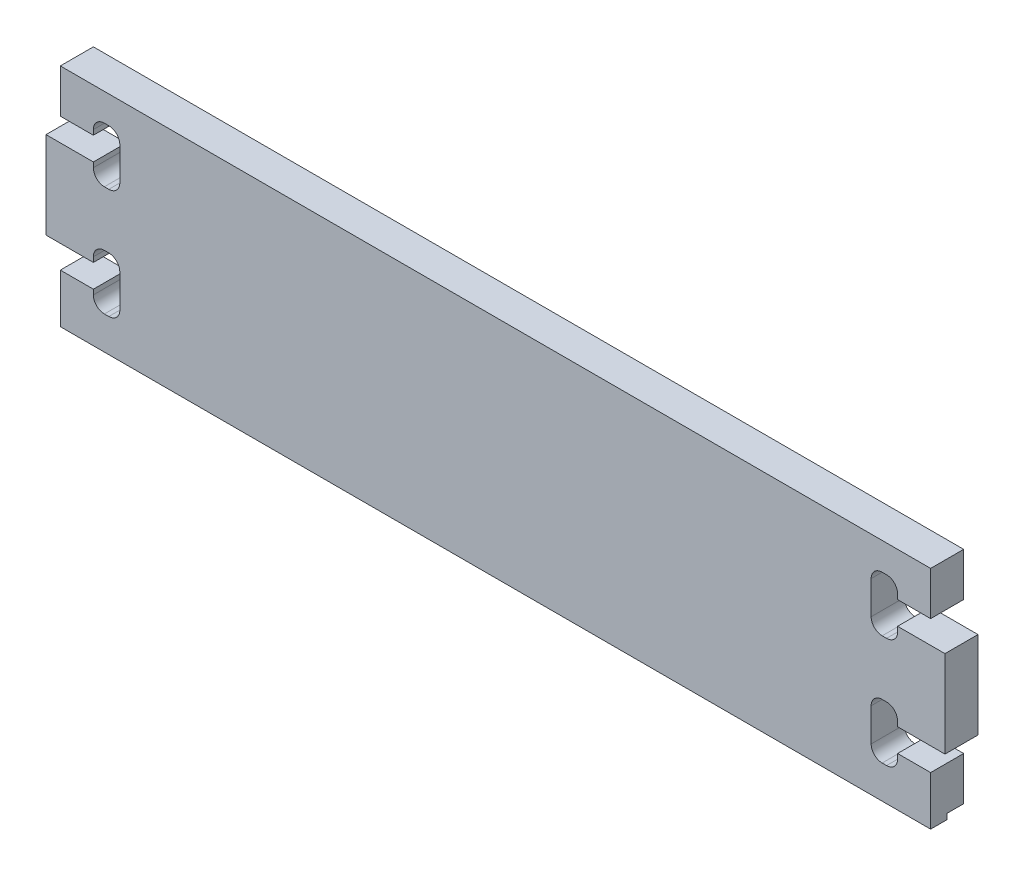
SolidWorks part; units mm, degrees
ref_plane "Front Plane" through (0, 0, 0) normal (0, 0, 1) x (1, 0, 0)
ref_plane "Top Plane" through (0, 0, 0) normal (0, 1, 0) x (1, 0, 0)
ref_plane "Right Plane" through (0, 0, 0) normal (1, 0, 0) x (0, 0, -1)
sketch "Sketch1" plane through (0, 0, 0) normal (0, 0, 1) x (1, 0, 0)
  line L0 (-39.5, 0) -> (39.5, 0) construction
  line L1 (-39.5, 10) -> (39.5, 10)
  line L2 (-39.5, 10) -> (-39.5, -10)
  line L3 (-39.5, -10) -> (39.5, -10)
  line L4 (39.5, 10) -> (39.5, -10)
  line L5 (-39.5, 10) -> (39.5, -10) construction
  line L6 (-39.5, -10) -> (39.5, 10) construction
  line L7 (0, 10) -> (0, -10) construction
  line L9 (-40.8, -3.95) -> (-39.5, -3.95)
  line L10 (-40.8, -3.95) -> (-40.8, 3.95)
  line L11 (-40.8, 3.95) -> (-39.5, 3.95)
  line L12 (-39.5, -3.95) -> (-39.5, 3.95)
  line L13 (-40.8, -3.95) -> (-39.5, 3.95) construction
  line L14 (-40.8, 3.95) -> (-39.5, -3.95) construction
  line L16 (40.8, 3.95) -> (39.5, 3.95)
  line L17 (40.8, -3.95) -> (40.8, 3.95)
  line L18 (40.8, -3.95) -> (39.5, -3.95)
  line L19 (-39.5, 5) -> (39.5, 5) construction
  line L20 (-35.3, 7.5) -> (-35.3, 2.5) construction
  line L21 (-36.5, 3.95) -> (-39.5, 3.95)
  line L22 (-36.5, 3.95) -> (-36.5, 6.05)
  line L23 (-36.5, 6.05) -> (-39.5, 6.05)
  line L24 (-39.5, 3.95) -> (-39.5, 6.05)
  line L25 (-36.5, 3.95) -> (-39.5, 6.05) construction
  line L26 (-36.5, 6.05) -> (-39.5, 3.95) construction
  line L27 (-34.1, 7.5) -> (-36.5, 7.5)
  line L28 (-34.1, 7.5) -> (-34.1, 2.5)
  line L29 (-34.1, 2.5) -> (-36.5, 2.5)
  line L30 (-36.5, 7.5) -> (-36.5, 2.5)
  line L31 (-34.1, 7.5) -> (-36.5, 2.5) construction
  line L32 (-34.1, 2.5) -> (-36.5, 7.5) construction
  line L33 (-34.1, -7.5) -> (-36.5, -7.5)
  line L34 (-34.1, -7.5) -> (-34.1, -2.5)
  line L35 (-34.1, -2.5) -> (-36.5, -2.5)
  line L36 (-36.5, -7.5) -> (-36.5, -2.5)
  line L37 (-36.5, -3.95) -> (-39.5, -3.95)
  line L38 (-36.5, -6.05) -> (-39.5, -6.05)
  line L39 (36.5, 3.95) -> (39.5, 3.95)
  line L40 (36.5, 6.05) -> (39.5, 6.05)
  line L41 (36.5, 7.5) -> (36.5, 2.5)
  line L42 (34.1, 7.5) -> (36.5, 7.5)
  line L43 (34.1, 7.5) -> (34.1, 2.5)
  line L44 (34.1, 2.5) -> (36.5, 2.5)
  line L45 (34.1, -2.5) -> (36.5, -2.5)
  line L46 (34.1, -7.5) -> (34.1, -2.5)
  line L47 (34.1, -7.5) -> (36.5, -7.5)
  line L48 (36.5, -7.5) -> (36.5, -2.5)
  line L49 (36.5, -6.05) -> (39.5, -6.05)
  line L50 (36.5, -3.95) -> (39.5, -3.95)
  point P0 (0, 0)
  point P10 (-40.15, 0)
  point P15 (-38, 5)
  point P35 (-35.3, 5)
  dimension "D1" = 79
  dimension "D2" = 20
  dimension "D4" = 1.3
  dimension "D7" = 5
  dimension "D8" = 2.1
  dimension "D9" = 3
  dimension "D10" = 2.4
  dimension "D11" = 5
extrude "Base shape" add sketch "Sketch1" along normal blind 3 contours L4 L1 L2 L3 | L9 L2 L11 L10 | L16 L4 L18 L17 region at (0, 0, 0) region at (-40.15, 0, 0) region at (40.15, 0, 0)
sketch "Sketch4" plane through (0, -10, 0) normal (0, -1, 0) x (1, 0, 0)
  line L0 (39.5, 3) -> (39.5, 0) construction
  line L1 (-39.5, 3) -> (39.5, 3)
  line L2 (-39.5, 3) -> (-39.5, 1.5)
  line L3 (-39.5, 1.5) -> (39.5, 1.5)
  line L4 (39.5, 3) -> (39.5, 1.5)
extrude "Floor lip" add sketch "Sketch4" along normal blind 0.5
sketch "Sketch6" plane through (0, 0, 0) normal (0, 0, -1) x (-1, 0, 0)
  line L0 (0, 0) -> (0, -10) construction
  line L1 (39.5, -10) -> (-39.5, -10) construction
  line L2 (-4, -10) -> (4, -10) construction
  line L3 (39.5, -10) -> (-39.5, -10) construction
  line L4 (-4, -9) -> (4, -9)
  line L5 (-4, -11) -> (4, -11)
  arc A0 (-4, -9) -> (-4, -11) centre (-4, -10) ccw
  arc A1 (4, -11) -> (4, -9) centre (4, -10) ccw
  point P9 (0, -10)
  dimension "D1" = 2
  dimension "D2" = 8
extrude "Nail cutout" cut sketch "Sketch6" against normal up to surface (1.5 mm away) up to face at (0, -10.25, 1.5)
sketch "Sketch3" plane through (-40.8, 0, 0) normal (-1, 0, 0) x (0, 0, 1)
  line L0 (0, 6.05) -> (3, 3.95) construction
  line L1 (0, 6.05) -> (3, 6.05)
  line L2 (0, 6.05) -> (0, 3.95)
  line L3 (0, 3.95) -> (3, 3.95)
  line L4 (3, 6.05) -> (3, 3.95)
  line L5 (0, -3.95) -> (3, -6.05) construction
  line L6 (0, -3.95) -> (3, -3.95)
  line L7 (0, -3.95) -> (0, -6.05)
  line L8 (0, -6.05) -> (3, -6.05)
  line L9 (3, -3.95) -> (3, -6.05)
  point P6 (1.5, 5)
  point P13 (1.5, -5)
ref_axis "Tap axis top" through (-53.7846, 5, 1.5) along (1, 0, 0)
ref_axis "Tap axis bottom" through (-54.2844, -5, 1.5) along (1, 0, 0)
fillet "Mill fillets" radius 1 16 edges at (36.5, -7.5, 1.5) (36.5, 2.5, 1.5) (34.1, 2.5, 1.5) (34.1, -7.5, 1.5) (36.5, -2.5, 1.5) (36.5, 7.5, 1.5) (34.1, -2.5, 1.5) (34.1, 7.5, 1.5) (-36.5, -2.5, 1.5) (-34.1, -2.5, 1.5) (-34.1, -7.5, 1.5) (-36.5, -7.5, 1.5) (-36.5, 2.5, 1.5) (-34.1, 2.5, 1.5) (-34.1, 7.5, 1.5) (-36.5, 7.5, 1.5)
